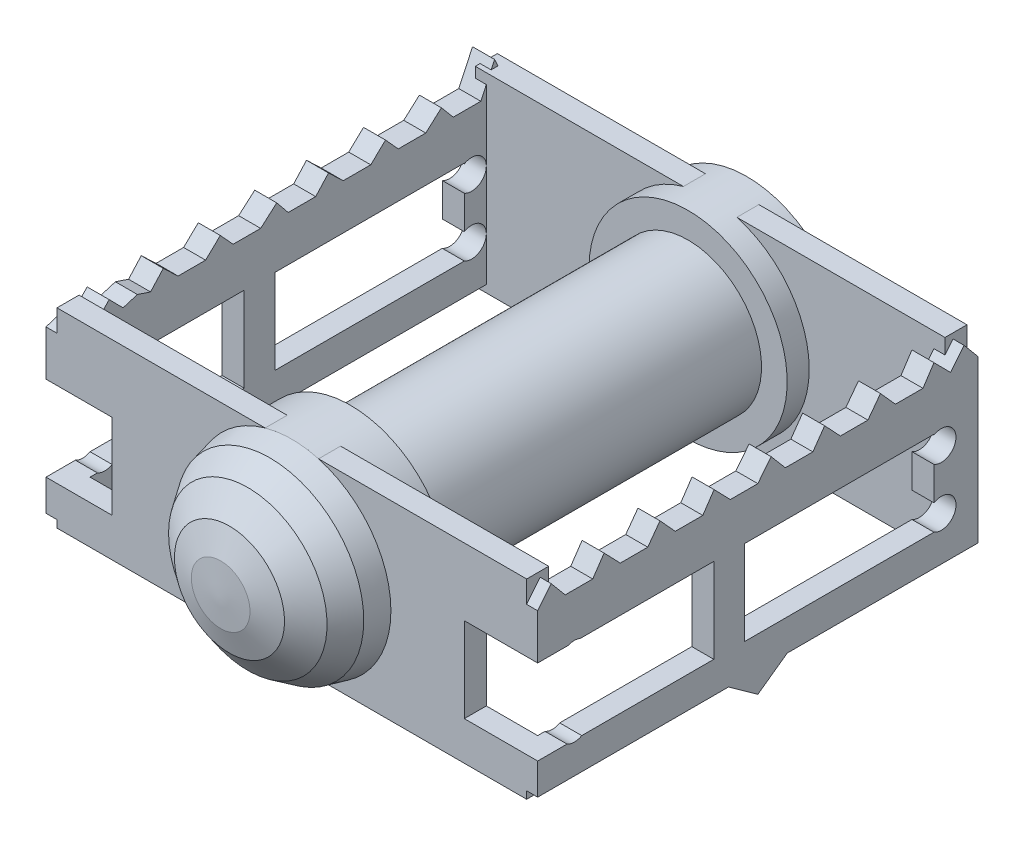
SolidWorks part; units mm, degrees
material "6061-T6 (SS)"
ref_plane "Alzado" through (0, 0, 0) normal (0, 0, 1) x (1, 0, 0)
ref_plane "Planta" through (0, 0, 0) normal (0, 1, 0) x (1, 0, 0)
ref_plane "Vista lateral" through (0, 0, 0) normal (1, 0, 0) x (0, 0, -1)
sketch "Sk_Eje_cuerpo" plane through (0, 0, 0) normal (0, 1, 0) x (1, 0, 0)
  line L0 (183.5, -84) -> (186, -84)
  line L1 (186, -84) -> (186, -92)
  line L2 (186, -92) -> (182.5, -92)
  line L3 (182.5, -92) -> (182.5, -138)
  line L4 (182.5, -138) -> (186, -138)
  line L5 (186, -138) -> (186, -146)
  line L6 (186, -146) -> (185.3, -149)
  line L7 (185.3, -149) -> (183.3, -152)
  line L8 (183.3, -152) -> (180, -154.5)
  line L9 (180, -154.5) -> (176.5, -155.7)
  line L10 (176.5, -155.7) -> (172.5, -156)
  line L11 (172.5, -156) -> (172.5, -147)
  line L12 (172.5, -147) -> (183.5, -147)
  line L13 (183.5, -147) -> (183.5, -138.5)
  line L14 (183.5, -138.5) -> (178.8, -138.5)
  line L15 (178.8, -138.5) -> (178.8, -91.5)
  line L16 (178.8, -91.5) -> (183.5, -91.5)
  line L17 (183.5, -91.5) -> (183.5, -84)
  line L18 (172.5, -62.1) -> (172.5, -160) construction
revolve "Eje_cuerpo" add sketch "Sk_Eje_cuerpo" angle 360 about L18
sketch "Sk_Placa_delantera" plane through (0, 0, 0) normal (1, 0, 0) x (0, 0, -1)
  line L0 (-86, -12) -> (-112, -12)
  line L1 (-112, -12) -> (-116, -14.8711)
  line L2 (-116, -14.8711) -> (-120, -12)
  line L3 (-120, -12) -> (-146, -12)
  line L4 (-146, -12) -> (-146, 10)
  line L5 (-146, 10) -> (-144.1582, 12.2815)
  line L6 (-144.1582, 12.2815) -> (-142.25, 10)
  line L7 (-142.25, 10) -> (-140.7929, 10)
  line L8 (-140.7929, 10) -> (-138.5, 10)
  line L9 (-138.5, 10) -> (-136.9468, 12.2815)
  line L10 (-136.9468, 12.2815) -> (-134.75, 10)
  line L11 (-134.75, 10) -> (-133.3411, 10)
  line L12 (-133.3411, 10) -> (-131, 10)
  line L13 (-131, 10) -> (-129.3348, 12.2815)
  line L14 (-129.3348, 12.2815) -> (-127.25, 10)
  line L15 (-127.25, 10) -> (-125.8092, 10)
  line L16 (-125.8092, 10) -> (-123.5, 10)
  line L17 (-123.5, 10) -> (-121.9631, 12.2815)
  line L18 (-121.9631, 12.2815) -> (-119.75, 10)
  line L19 (-119.75, 10) -> (-117.9568, 10)
  line L20 (-117.9568, 10) -> (-116, 10)
  line L21 (-116, 10) -> (-114.1908, 12.2815)
  line L22 (-114.1908, 12.2815) -> (-112.25, 10)
  line L23 (-112.25, 10) -> (-110.6652, 10)
  line L24 (-110.6652, 10) -> (-108.5, 10)
  line L25 (-108.5, 10) -> (-106.8993, 12.2815)
  line L26 (-106.8993, 12.2815) -> (-104.75, 10)
  line L27 (-104.75, 10) -> (-103.0532, 10)
  line L28 (-103.0532, 10) -> (-101, 10)
  line L29 (-101, 10) -> (-99.2872, 12.2815)
  line L30 (-99.2872, 12.2815) -> (-97.25, 10)
  line L31 (-97.25, 10) -> (-95.6014, 10)
  line L32 (-95.6014, 10) -> (-93.5, 10)
  line L33 (-93.5, 10) -> (-92, 12.2815)
  line L34 (-92, 12.2815) -> (-89.75, 10)
  line L35 (-89.75, 10) -> (-87.9092, 12.2815)
  line L36 (-87.9092, 12.2815) -> (-86, 10)
  line L37 (-86, 10) -> (-86, -12)
  line L38 (-92, 13.5) -> (-92, -13.5) construction
  point P38 (-116, -14.8711)
  point P39 (-95.6014, 10)
  point P40 (-103.0532, 10)
  point P41 (-110.6652, 10)
  point P42 (-117.9568, 10)
  point P43 (-125.8092, 10)
  point P44 (-133.3411, 10)
  point P45 (-140.7929, 10)
  point P46 (-114.1908, 12.2815)
  point P47 (-121.9631, 12.2815)
  point P48 (-129.3348, 12.2815)
  point P49 (-136.9468, 12.2815)
  point P50 (-106.8993, 12.2815)
  point P51 (-99.2872, 12.2815)
  point P52 (-92, 12.2815)
  point P55 (-87.9092, 12.2815)
  point P56 (-144.1582, 12.2815)
extrude "Placa_delantera" add sketch "Sk_Placa_delantera" along normal blind 3 from offset 203
sketch3d "Sk_Agujero_Placa_delantera_1"
  line L0 (201.5, -6, 91) -> (207.5, -6, 91)
  dimension "D1" = 6
sweep "Agujero_Placa_delantera_1" cut path "Sk_Agujero_Placa_delantera_1" circular profile diameter 4 parameters "D3"=4
sketch3d "Sk_Agujero_Placa_delantera_2"
  line L0 (201.5, 2, 91) -> (207.5, 2, 91)
  dimension "D1" = 6
sweep "Agujero_Placa_delantera_2" cut path "Sk_Agujero_Placa_delantera_2" circular profile diameter 4 parameters "D3"=4
sketch3d "Sk_Agujero_Placa_delantera_3"
  line L0 (201.5, -6, 141) -> (207.5, -6, 141)
  dimension "D1" = 6
sweep "Agujero_Placa_delantera_3" cut path "Sk_Agujero_Placa_delantera_3" circular profile diameter 4 parameters "D3"=4
sketch3d "Sk_Agujero_Placa_delantera_4"
  line L0 (201.5, 2, 141) -> (207.5, 2, 141)
  dimension "D1" = 6
sweep "Agujero_Placa_delantera_4" cut path "Sk_Agujero_Placa_delantera_4" circular profile diameter 4 parameters "D3"=4
sketch "Sk_Placa_trasera" plane through (0, 0, 0) normal (1, 0, 0) x (0, 0, -1)
  line L0 (-86, -12) -> (-146, -12)
  line L1 (-146, -12) -> (-146, 10)
  line L2 (-146, 10) -> (-144.1582, 10.5947)
  line L3 (-144.1582, 10.5947) -> (-142.25, 10)
  line L4 (-142.25, 10) -> (-140.3923, 11.9141)
  line L5 (-140.3923, 11.9141) -> (-138.5, 10)
  line L6 (-138.5, 10) -> (-136.5462, 10.5947)
  line L7 (-136.5462, 10.5947) -> (-134.75, 10)
  line L8 (-134.75, 10) -> (-133.0206, 11.9141)
  line L9 (-133.0206, 11.9141) -> (-131, 10)
  line L10 (-131, 10) -> (-129.0143, 10)
  line L11 (-129.0143, 10) -> (-127.25, 10)
  line L12 (-127.25, 10) -> (-125.2483, 11.9141)
  line L13 (-125.2483, 11.9141) -> (-123.5, 10)
  line L14 (-123.5, 10) -> (-121.242, 10)
  line L15 (-121.242, 10) -> (-119.75, 10)
  line L16 (-119.75, 10) -> (-117.5561, 11.9141)
  line L17 (-117.5561, 11.9141) -> (-116, 10)
  line L18 (-116, 10) -> (-113.7902, 10)
  line L19 (-113.7902, 10) -> (-112.25, 10)
  line L20 (-112.25, 10) -> (-110.505, 11.9141)
  line L21 (-110.505, 11.9141) -> (-108.5, 10)
  line L22 (-108.5, 10) -> (-106.4986, 10)
  line L23 (-106.4986, 10) -> (-104.75, 10)
  line L24 (-104.75, 10) -> (-102.7327, 11.9141)
  line L25 (-102.7327, 11.9141) -> (-101, 10)
  line L26 (-101, 10) -> (-98.6462, 10)
  line L27 (-98.6462, 10) -> (-97.25, 10)
  line L28 (-97.25, 10) -> (-95.1206, 11.9141)
  line L29 (-95.1206, 11.9141) -> (-93.5, 10)
  line L30 (-93.5, 10) -> (-91.2746, 10)
  line L31 (-91.2746, 10) -> (-89.75, 10)
  line L32 (-89.75, 10) -> (-87.875, 14)
  line L33 (-87.875, 14) -> (-86, 10)
  line L34 (-86, 10) -> (-86, -12)
  point P35 (-144.1582, 10.5947)
  point P36 (-136.5462, 10.5947)
  point P37 (-129.0143, 10)
  point P38 (-121.242, 10)
  point P39 (-113.7902, 10)
  point P40 (-106.4986, 10)
  point P41 (-98.6462, 10)
  point P42 (-91.2746, 10)
  point P43 (-125.2483, 11.9141)
  point P44 (-133.0206, 11.9141)
  point P45 (-140.3923, 11.9141)
  point P46 (-110.505, 11.9141)
  point P47 (-102.7327, 11.9141)
  point P48 (0, 0)
  point P49 (-95.1206, 11.9141)
  point P50 (-117.5561, 11.9141)
extrude "Placa_trasera" add sketch "Sk_Placa_trasera" along normal blind 3 from offset 139
sketch3d "Sk_Agujero_Placa_trasera_1"
  line L0 (137.5, -6, 91) -> (143.5, -6, 91)
  dimension "D1" = 6
sweep "Agujero_Placa_trasera_1" cut path "Sk_Agujero_Placa_trasera_1" circular profile diameter 4 parameters "D3"=4
sketch3d "Sk_Agujero_Placa_trasera_2"
  line L0 (137.5, 2, 91) -> (143.5, 2, 91)
  dimension "D1" = 6
sweep "Agujero_Placa_trasera_2" cut path "Sk_Agujero_Placa_trasera_2" circular profile diameter 4 parameters "D3"=4
sketch3d "Sk_Agujero_Placa_trasera_3"
  line L0 (137.5, -6, 141) -> (143.5, -6, 141)
  dimension "D1" = 6
sweep "Agujero_Placa_trasera_3" cut path "Sk_Agujero_Placa_trasera_3" circular profile diameter 4 parameters "D3"=4
sketch3d "Sk_Agujero_Placa_trasera_4"
  line L0 (137.5, 2, 141) -> (143.5, 2, 141)
  dimension "D1" = 6
sweep "Agujero_Placa_trasera_4" cut path "Sk_Agujero_Placa_trasera_4" circular profile diameter 4 parameters "D3"=4
sketch "Sk_Marco_interior" plane through (0, 0, 0) normal (0, 0, 1) x (1, 0, 0)
  line L0 (140.5, -13) -> (204.5, -13)
  line L1 (204.5, -13) -> (204.5, 13)
  line L2 (204.5, 13) -> (140.5, 13)
  line L3 (140.5, 13) -> (140.5, -13)
  circle A0 centre (172.5, 0) radius 11
  dimension "DIAM1" = 22
extrude "Marco_interior" add sketch "Sk_Marco_interior" along normal blind 3 from offset 86
sketch "Sk_Marco_exterior" plane through (0, 0, 0) normal (0, 0, 1) x (1, 0, 0)
  line L0 (140.5, -13) -> (204.5, -13)
  line L1 (204.5, -13) -> (204.5, 13)
  line L2 (204.5, 13) -> (140.5, 13)
  line L3 (140.5, 13) -> (140.5, -13)
  circle A0 centre (172.5, 0) radius 11
  dimension "DIAM2" = 22
extrude "Marco_exterior" add sketch "Sk_Marco_exterior" along normal blind 3 from offset 143
ref_axis "Eje_pedal" through (172.5, 0, 146) along (0, 0, -1)
sketch "Croquis17" plane through (206, 0, 0) normal (1, 0, 0) x (0, 0, -1)
  line L0 (-92, 3.8293) -> (-117.7956, 3.8293)
  line L1 (-92, 10) -> (-92, -10) construction
  line L2 (-92, 13.5) -> (-92, -13.5) construction
  line L3 (-117.7956, 3.8293) -> (-117.7956, -7.7321)
  line L4 (-117.7956, -7.7321) -> (-92, -7.7321)
  line L5 (-92, -7.7321) -> (-92, 3.8293)
  circle A0 centre (-91, -6) radius 2 construction
extrude "Cortar-Extruir1" cut sketch "Croquis17" against normal blind 10
ref_plane "Plano1" through (172, 0, 0) normal (1, 0, 0) x (0, 0, -1)
mirror "Simetría1" about plane through (172, 0, 0) normal (1, 0, 0) of "Cortar-Extruir1"
pattern_linear "MatrizL1" count 2 spacing 30 along (0, 0, 1) of "Simetría1"
